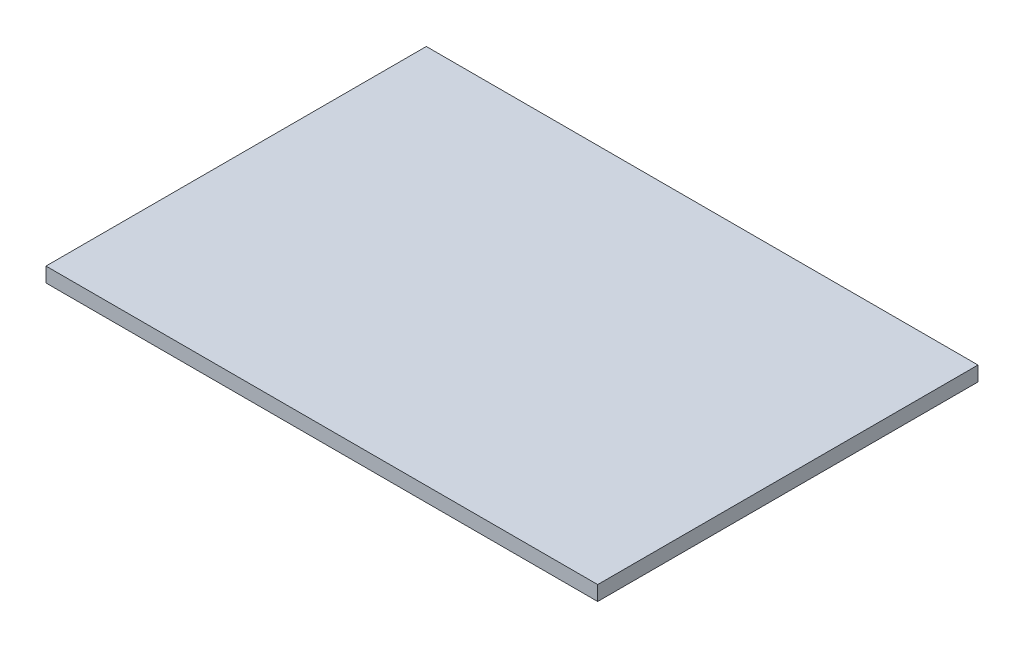
SolidWorks part; units mm, degrees
ref_plane "Front Plane" through (0, 0, 0) normal (0, 0, 1) x (1, 0, 0)
ref_plane "Top Plane" through (0, 0, 0) normal (0, 1, 0) x (1, 0, 0)
ref_plane "Right Plane" through (0, 0, 0) normal (1, 0, 0) x (0, 0, -1)
sketch "Sketch1" plane through (0, 0, 0) normal (0, 1, 0) x (1, 0, 0)
  line L1 (-169, -116.5) -> (169, -116.5)
  line L2 (-169, -116.5) -> (-169, 116.5)
  line L3 (-169, 116.5) -> (169, 116.5)
  line L4 (169, -116.5) -> (169, 116.5)
  line L5 (-169, -116.5) -> (169, 116.5) construction
  line L6 (-169, 116.5) -> (169, -116.5) construction
  point P0 (0, 0)
  dimension "D2" = 233
  dimension "D1" = 338
extrude "Boss-Extrude1" add sketch "Sketch1" along normal blind 9
equation "\"PCLength\"= 320mm'Length across I/O from PS to GPU"
equation "\"PCWidth\"= 242mm'Distance of longest part parallel to GPU(ussually GPU)"
equation "\"PCHeight\"= 172mm'Tallest point with mobo laying flat"
equation "\"WallThickness\"= 9mm'Thickness of each outer tank wall"
equation "\"ThermoBarrierThickness\"= 3mm'Thickness of barrier between hot side and cold side"
equation "\"HotSideGap\"= 40mm'Space in the hot side for a pump"
equation "\"PCClearance\"= 30mm'Clearance from top of tank to top of PC"
equation "\"RadiatorHeight\"= 275mm'Final Height from ground of radiators"
equation "\"D2@Sketch1\"=\"PCHeight\" + \"ThermoBarrierThickness\" + \"HotSideGap\" + (2 * \"WallThickness\")"
equation "\"D1@Boss-Extrude1\"=\"WallThickness\""
